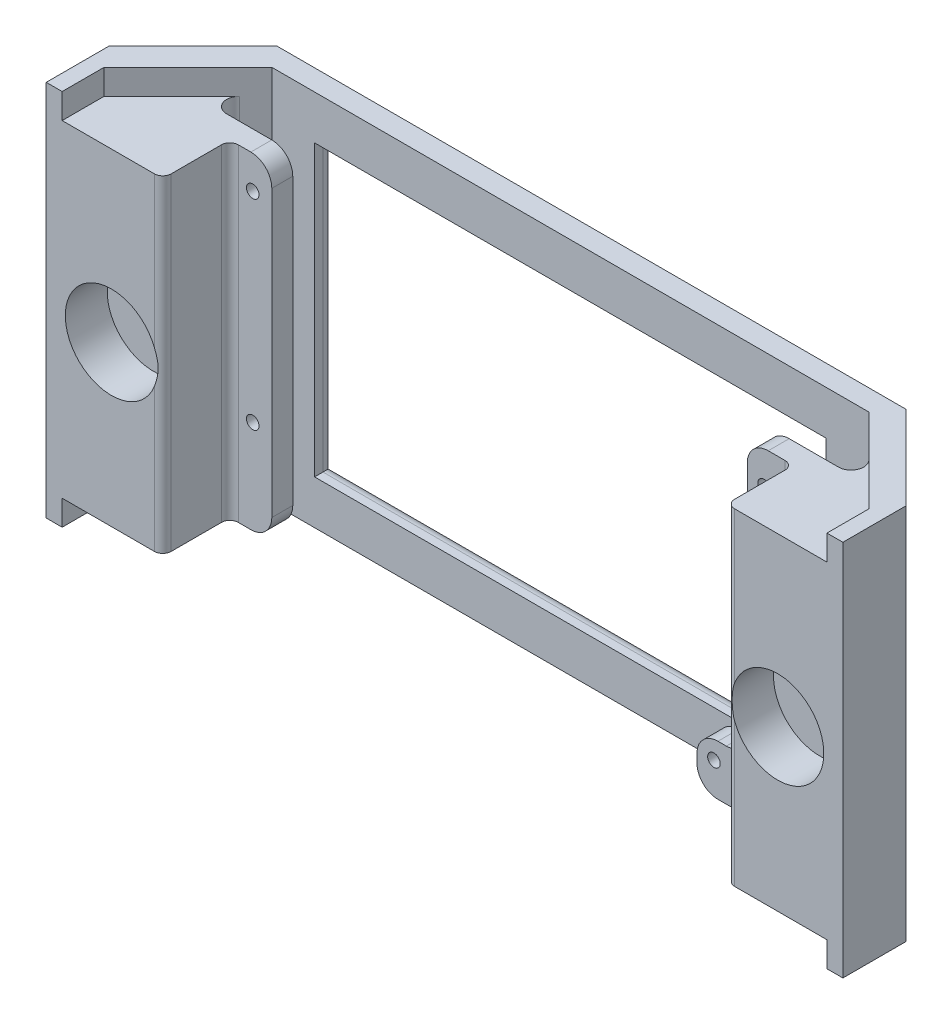
SolidWorks part; units mm, degrees
ref_plane "Front Plane" through (0, 0, 0) normal (0, 0, 1) x (1, 0, 0)
ref_plane "Top Plane" through (0, 0, 0) normal (0, 1, 0) x (1, 0, 0)
ref_plane "Right Plane" through (0, 0, 0) normal (1, 0, 0) x (0, 0, -1)
sketch "Sketch1" plane through (0, 0, 0) normal (0, 0, 1) x (1, 0, 0)
  line L1 (-95, 45) -> (95, 45)
  line L2 (-95, 45) -> (-95, -45)
  line L3 (-95, -45) -> (95, -45)
  line L4 (95, 45) -> (95, -45)
  line L5 (-95, 45) -> (95, -45) construction
  line L6 (-95, -45) -> (95, 45) construction
  line L7 (-61, 34.5) -> (61, 34.5)
  line L8 (-61, 34.5) -> (-61, -34.5)
  line L9 (-61, -34.5) -> (61, -34.5)
  line L10 (61, 34.5) -> (61, -34.5)
  line L11 (-61, 34.5) -> (61, -34.5) construction
  line L12 (-61, -34.5) -> (61, 34.5) construction
  point P0 (0, 0)
  point P6 (0, 0)
  dimension "D1" = 122
  dimension "D2" = 190
  dimension "D3" = 69
  dimension "D4" = 90
extrude "Boss-Extrude1" add sketch "Sketch1" along normal blind 5
sketch "Sketch2" plane through (0, 0, 5) normal (0, 0, 1) x (1, 0, 0)
  line L0 (-95, -45) -> (95, -45) construction
  line L1 (-95, 45) -> (-91.2, 45)
  line L2 (-95, 45) -> (-95, -45)
  line L3 (-95, -45) -> (-91.2, -45)
  line L4 (-91.2, 45) -> (-91.2, -45)
  line L5 (0, 0) -> (0, 45) construction
  line L6 (95, 45) -> (-95, 45) construction
  line L7 (95, -45) -> (91.2, -45)
  line L8 (91.2, 45) -> (91.2, -45)
  line L9 (95, 45) -> (91.2, 45)
  line L10 (95, 45) -> (95, -45)
  dimension "D1" = 3.8
extrude "Boss-Extrude2" add sketch "Sketch2" along normal blind 30
sketch "Sketch3" plane through (0, 45, 0) normal (0, 1, 0) x (1, 0, 0)
  line L0 (-91.2, -35) -> (-91.2, -5) construction
  line L1 (-91.2, -14) -> (-57.2, -14)
  line L2 (-91.2, -14) -> (-91.2, -19)
  line L3 (-91.2, -19) -> (-57.2, -19)
  line L4 (-57.2, -14) -> (-57.2, -19)
  line L5 (91.2, -35) -> (91.2, -5) construction
  line L6 (91.2, -14) -> (44.2, -14)
  line L7 (91.2, -14) -> (91.2, -19)
  line L8 (91.2, -19) -> (44.2, -19)
  line L9 (44.2, -14) -> (44.2, -19)
  line L10 (91.2, -5) -> (-91.2, -5) construction
  dimension "D1" = 9
  dimension "D2" = 9
  dimension "D3" = 5
  dimension "D4" = 5
  dimension "D5" = 34
  dimension "D6" = 47
extrude "Boss-Extrude3" add sketch "Sketch3" against normal up to surface (90 mm away) up to face at (0, -45, 18.75)
sketch "Sketch4" plane through (0, 0, 19) normal (0, 0, 1) x (1, 0, 0)
  line L0 (91.2, -45) -> (91.2, 45) construction
  line L1 (-91.2, 45) -> (91.2, 45)
  line L2 (-91.2, 45) -> (-91.2, 39)
  line L3 (-91.2, 39) -> (91.2, 39)
  line L4 (91.2, 45) -> (91.2, 39)
  line L5 (0, 0) -> (-91.2, 0) construction
  line L6 (-91.2, -45) -> (-91.2, 45) construction
  line L7 (-91.2, -39) -> (91.2, -39)
  line L8 (91.2, -45) -> (91.2, -39)
  line L9 (-91.2, -45) -> (91.2, -45)
  line L10 (-91.2, -45) -> (-91.2, -39)
  dimension "D1" = 6
extrude "Cut-Extrude1" cut sketch "Sketch4" against normal blind 5
sketch "Sketch5" plane through (0, 0, 19) normal (0, 0, 1) x (1, 0, 0)
  line L0 (0, 0) -> (-61.75, 0) construction
  line L1 (-70.2, 37.38) -> (70.2, 37.38) construction
  line L2 (-70.2, 37.38) -> (-70.2, -37.38) construction
  line L3 (-70.2, -37.38) -> (70.2, -37.38) construction
  line L4 (70.2, 37.38) -> (70.2, -37.38) construction
  line L5 (-70.2, 37.38) -> (70.2, -37.38) construction
  line L6 (-70.2, -37.38) -> (70.2, 37.38) construction
  line L7 (-61.75, 0) -> (-61.75, 31.13) construction
  line L8 (-61.75, 0) -> (-61.75, -16.61) construction
  line L9 (48.25, 0) -> (60.23, 0) construction
  line L10 (60.23, 0) -> (60.23, 31.13) construction
  line L11 (0, 0) -> (48.25, 0) construction
  line L12 (48.25, 0) -> (48.25, -31.38) construction
  circle A0 centre (-61.75, 31.13) radius 1.5
  circle A1 centre (-61.75, -16.61) radius 1.5
  circle A2 centre (60.23, 31.13) radius 1.5
  circle A3 centre (48.25, -31.38) radius 1.5
  point P0 (0, 0)
  dimension "D10" = 3
  dimension "D11" = 3
  dimension "D12" = 3
  dimension "D13" = 3
  dimension "D1" = 140.4
  dimension "D2" = 74.76
  dimension "D3" = 61.75
  dimension "D4" = 31.13
  dimension "D5" = 16.61
  dimension "D6" = 60.23
  dimension "D7" = 31.13
  dimension "D8" = 48.25
  dimension "D9" = 31.38
extrude "Cut-Extrude2" cut sketch "Sketch5" against normal up to surface (5 mm away) up to face at (67.7, 0, 14)
sketch "Sketch6" plane through (0, 0, 19) normal (0, 0, 1) x (1, 0, 0)
  line L1 (44.2, 39) -> (56.2, 39)
  line L2 (44.2, 39) -> (44.2, -27)
  line L3 (44.2, -27) -> (56.2, -27)
  line L4 (56.2, 39) -> (56.2, -27)
  dimension "D1" = 12
  dimension "D2" = 66
extrude "Cut-Extrude3" cut sketch "Sketch6" against normal up to surface (5 mm away) up to face at (46.75, -31.38, 14)
fillet "Fillet3" radius 3 4 edges at (-61, 0, 0) (0, -34.5, 0) (61, 0, 0) (0, 34.5, 0)
chamfer "Chamfer6" distance 20 angle 45 4 edges at (91.2, 0, 5) (95, 0, 0) (-95, 0, 0) (-91.2, 0, 5)
sketch "Sketch7" plane through (0, 39, 0) normal (0, 1, 0) x (1, 0, 0)
  line L0 (-85.2, -19) -> (-91.2, -25)
  line L1 (-91.2, -25) -> (-91.2, -35)
  line L2 (-91.2, -35) -> (-67.2, -35)
  line L3 (-67.2, -35) -> (-67.2, -19)
  line L4 (-85.2, -19) -> (-57.2, -19) construction
  line L5 (-67.2, -19) -> (-85.2, -19)
  line L6 (0, 0) -> (0, -5) construction
  line L7 (71.2, -5) -> (-71.2, -5) construction
  line L8 (67.2, -35) -> (67.2, -19)
  line L9 (91.2, -35) -> (67.2, -35)
  line L10 (91.2, -25) -> (91.2, -35)
  line L11 (85.2, -19) -> (91.2, -25)
  line L12 (67.2, -19) -> (85.2, -19)
  dimension "D1" = 24
extrude "Boss-Extrude4" add sketch "Sketch7" against normal up to surface (78 mm away) up to face at (-69.95, -39, 16.5)
fillet "Fillet4" radius 5 6 edges at (-57.2, -39, 16.5) (-57.2, 39, 16.5) (56.2, 39, 16.5) (44.2, -39, 16.5) (44.2, -27, 16.5) (56.2, -27, 16.5)
fillet "Fillet5" radius 2 4 edges at (-67.2, 0, 35) (67.2, 0, 35) (67.2, 0, 19) (-67.2, 0, 19)
fillet "Fillet6" radius 3 2 edges at (-80.2, 0, 14) (80.2, 0, 14)
sketch "Sketch9" plane through (0, 0, 35) normal (0, 0, 1) x (1, 0, 0)
  line L6 (0, 0) -> (0, -45) construction
  line L7 (-71.2, -45) -> (71.2, -45) construction
  line L8 (-95, 45) -> (-95, -45) construction
  line L9 (-95, 39) -> (-79.45, 39) construction
  line L10 (-95, 39) -> (-95, -0.9074) construction
  line L11 (-95, -0.9074) -> (-79.45, -0.9074) construction
  line L12 (-79.45, 39) -> (-79.45, -0.9074) construction
  line L13 (-91.2, 39) -> (-69.2, 39) construction
  circle A0 centre (-79.45, -0.9074) radius 11
  circle A1 centre (79.45, -0.9074) radius 11
  dimension "D3" = 22
  dimension "D1" = 39.9074
  dimension "D2" = 15.55
extrude "Cut-Extrude4" cut sketch "Sketch9" against normal blind 10
